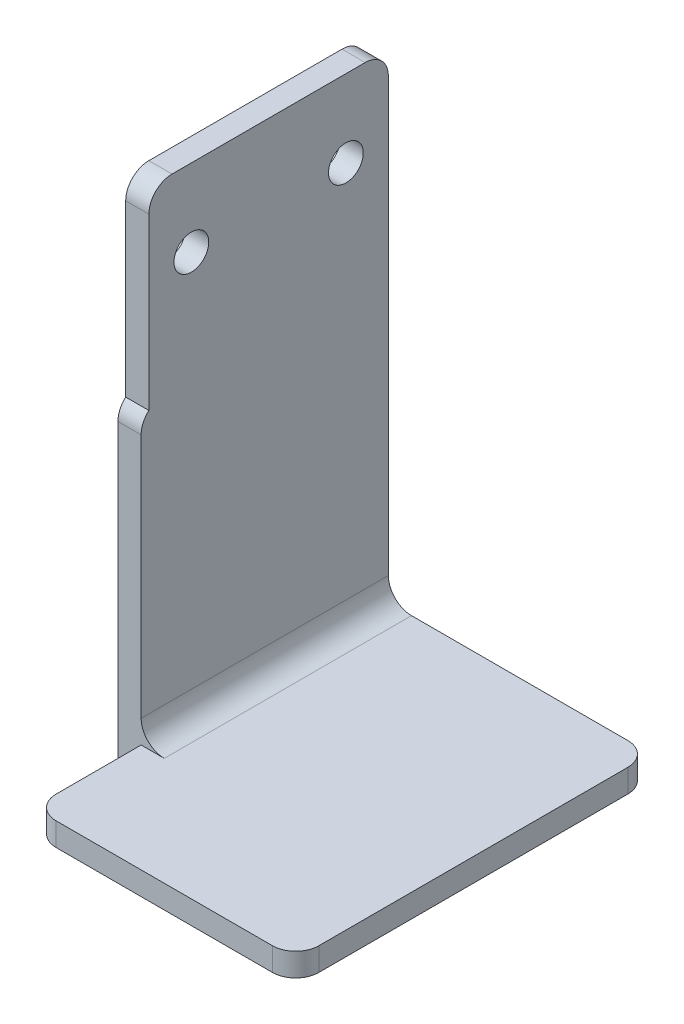
SolidWorks part; units mm, degrees
ref_plane "Front Plane" through (0, 0, 0) normal (0, 0, 1) x (1, 0, 0)
ref_plane "Top Plane" through (0, 0, 0) normal (0, 1, 0) x (1, 0, 0)
ref_plane "Right Plane" through (0, 0, 0) normal (1, 0, 0) x (0, 0, -1)
sketch "Sketch1" plane through (0, 0, 0) normal (0, 0, 1) x (1, 0, 0)
  line L0 (0, 0) -> (0, 65)
  line L1 (0, 65) -> (3, 65)
  line L2 (3, 65) -> (3, 3)
  line L3 (3, 3) -> (37, 3)
  line L4 (37, 3) -> (37, 0)
  line L5 (37, 0) -> (0, 0)
  dimension "D1" = 3
  dimension "D2" = 3
  dimension "D3" = 65
  dimension "D4" = 37
extrude "Boss-Extrude1" add sketch "Sketch1" along normal blind 46
sketch "Sketch2" plane through (0, 0, 0) normal (-1, 0, 0) x (0, 0, 1)
  line L0 (46, 0) -> (0, 0) construction
  line L1 (32, 65) -> (46, 65)
  line L3 (32, 0) -> (46, 0)
  line L4 (46, 65) -> (46, 0) construction
  line L5 (32, 65) -> (46, 0) construction
  line L6 (32, 0) -> (46, 65) construction
  line L7 (46, 65) -> (46, 0) construction
  line L8 (46, 0) -> (46, 65)
  line L9 (46, 65) -> (0, 65) construction
  line L10 (32, 65) -> (0, 65) construction
  line L12 (32, 0) -> (32, 40)
  line L13 (32, 40) -> (31, 40)
  line L14 (31, 40) -> (31, 65)
  line L15 (31, 65) -> (32, 65)
  point P4 (39, 32.5)
  dimension "D1" = 32
  dimension "D2" = 25
  dimension "D3" = 1
extrude "Cut-Extrude1" cut sketch "Sketch2" against normal up to vertex (3 mm away) up to point (3, 3, 0)
sketch "Sketch3" plane through (3, 0, 0) normal (1, 0, 0) x (0, 0, -1)
  line L0 (-31, 65) -> (0, 65) construction
  line L3 (-15.5, 65) -> (-15.5, 55) construction
  line L4 (-25.5, 55) -> (-5.5, 55) construction
  circle A0 centre (-25.5, 55) radius 2.25
  circle A1 centre (-5.5, 55) radius 2.25
  point P0 (-16, 65)
  point P10 (-15.5, 55)
  point P12 (-14, 65)
  dimension "D2" = 4.5
  dimension "D1" = 20
  dimension "D3" = 10
extrude "Cut-Extrude2" cut sketch "Sketch3" against normal blind 46
fillet "Fillet1" radius 3 7 edges at (37, 1.5, 46) (37, 1.5, 0) (3, 1.5, 46) (1.5, 65, 0) (3, 3, 16) (1.5, 40, 32) (1.5, 65, 31)
